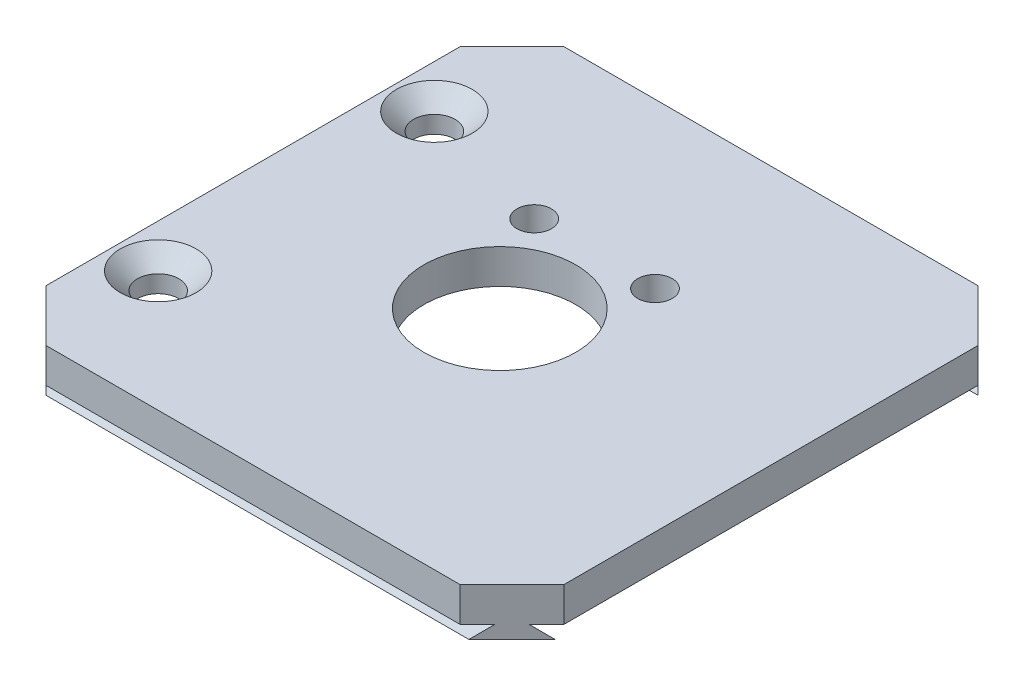
SolidWorks part; units mm, degrees
ref_plane "Front Plane" through (0, 0, 0) normal (0, 0, 1) x (1, 0, 0)
ref_plane "Top Plane" through (0, 0, 0) normal (0, 1, 0) x (1, 0, 0)
ref_plane "Right Plane" through (0, 0, 0) normal (1, 0, 0) x (0, 0, -1)
sketch "Sketch1" plane through (0, 0, 0) normal (0, 1, 0) x (1, 0, 0)
  line L0 (-11.2931, 29.7045) -> (12.7069, 29.7045)
  line L1 (12.7069, 29.7045) -> (15.7069, 26.7045)
  line L2 (15.7069, 26.7045) -> (15.7069, 2.7045)
  line L3 (15.7069, 2.7045) -> (12.7069, -0.2955)
  line L4 (12.7069, -0.2955) -> (-11.2931, -0.2955)
  line L5 (-11.2931, -0.2955) -> (-14.2931, 2.7045)
  line L6 (-14.2931, 26.7045) -> (-14.2931, 2.7045)
  line L7 (-11.2931, 29.7045) -> (-14.2931, 26.7045)
extrude "Boss-Extrude1" add sketch "Sketch1" along normal blind 2
sketch "Sketch2" plane through (0, 2, 0) normal (0, 1, 0) x (1, 0, 0)
  circle A0 centre (0, 14.7045) radius 4.4
  dimension "D1" = 8.8
extrude "Cut-Extrude1" cut sketch "Sketch2" against normal through all
sketch "Sketch5" plane through (0, 2, 0) normal (0, 1, 0) x (1, 0, 0)
  line L0 (-14.2931, 26.7045) -> (-14.2931, 2.7045) construction
  circle A0 centre (-3.5084, 20.2045) radius 1
  circle A1 centre (3.4916, 20.2045) radius 1
  dimension "D1" = 2
  dimension "D2" = 10.7846
  dimension "D3" = 17.7846
  dimension "D4" = 6.5
extrude "Cut-Extrude2" cut sketch "Sketch5" against normal up to next
sketch "Sketch7" plane through (0, 2, 0) normal (0, 1, 0) x (1, 0, 0)
  line L0 (12.7069, 29.7045) -> (-11.2931, 29.7045) construction
  line L1 (-11.2931, -0.2955) -> (12.7069, -0.2955) construction
  line L3 (-14.2931, 26.7045) -> (-14.2931, 2.7045) construction
  circle A0 centre (-11.7931, 22.7045) radius 1
  circle A1 centre (-11.7931, 6.7045) radius 1
  point P0 (-11.7931, 22.7045)
  point P2 (-11.7931, 6.7045)
  dimension "D5" = 2
  dimension "D6" = 2
  dimension "D1" = 7
  dimension "D2" = 7
  dimension "D3" = 2.5
  dimension "D4" = 2.5
hole_wizard "CSK for M2 Flat Head Machine Screw2" positions "Sketch7" profile "Sketch8" countersink size "M2" standard "ANSI Metric"
sketch "Sketch8" plane through (-11.7931, 2, -22.7045) normal (1, 0, 0) x (0, 0, 1)
  line L0 (0, 0) -> (0, 43.651)
  line L1 (0, 43.651) -> (1.2, 42.93)
  line L2 (1.2, 42.93) -> (1.2, 1)
  line L3 (1.2, 1) -> (2.2, 0)
  line L5 (2.2, 0) -> (0, 0)
  line L6 (-1.2, 1) -> (-2.2, 0) construction
  line L10 (0, 43.651) -> (-1.2, 42.93) construction
  line L11 (0, -6.35) -> (0, 107.95) construction
  dimension "Hole Dia." = 2.4
  dimension "Hole Depth" = 42.93
  dimension "Near C'Sink Dia." = 4.4
  dimension "Near C'Sink Angle" = 90
  dimension "Drill Angle" = 118
sketch "Sketch10" plane through (15.7069, 0, 0) normal (1, 0, 0) x (0, 0, -1)
  line L0 (14.7045, 2) -> (14.7045, 0) construction
  line L1 (2.7045, 2) -> (26.7045, 2) construction
  line L2 (2.7045, 0) -> (26.7045, 0) construction
  line L3 (1.7045, 0) -> (2.4545, -0.75)
  line L4 (2.4545, -0.75) -> (-0.0455, -0.75)
  line L5 (-0.0455, -0.75) -> (0.7045, 0)
  line L6 (0.7045, 0) -> (1.7045, 0)
  line L8 (28.7045, 0) -> (27.7045, 0)
  line L9 (29.4545, -0.75) -> (28.7045, 0)
  line L10 (26.9545, -0.75) -> (29.4545, -0.75)
  line L11 (27.7045, 0) -> (26.9545, -0.75)
  dimension "D1" = 1
  dimension "D2" = 1
  dimension "D3" = 45
  dimension "D4" = 45
  dimension "D5" = 2.5
  dimension "D6" = 1
extrude "Boss-Extrude2" add sketch "Sketch10" against normal up to surface (30 mm away) up to face at (-14.2931, 1, -14.7045)
sketch "Sketch11" plane through (0, 2, 0) normal (0, 1, 0) x (1, 0, 0)
  line L0 (-14.2931, 26.7045) -> (-11.2931, 29.7045)
  line L1 (-11.2931, 29.7045) -> (12.7069, 29.7045)
  line L2 (12.7069, 29.7045) -> (15.7069, 26.7045)
  line L3 (15.7069, 26.7045) -> (15.7069, 2.7045)
  line L4 (15.7069, 2.7045) -> (12.7069, -0.2955)
  line L5 (12.7069, -0.2955) -> (-11.2931, -0.2955)
  line L6 (-11.2931, -0.2955) -> (-14.2931, 2.7045)
  line L7 (-14.2931, 2.7045) -> (-14.2931, 26.7045)
  line L8 (-24.2931, -1.4376) -> (-24.2931, 30.8467)
  line L9 (-24.2931, 30.8467) -> (-15.4352, 39.7045)
  line L10 (-15.4352, 39.7045) -> (16.8491, 39.7045)
  line L11 (16.8491, 39.7045) -> (25.7069, 30.8467)
  line L12 (25.7069, 30.8467) -> (25.7069, -1.4376)
  line L13 (25.7069, -1.4376) -> (16.8491, -10.2955)
  line L14 (16.8491, -10.2955) -> (-15.4352, -10.2955)
  line L15 (-15.4352, -10.2955) -> (-24.2931, -1.4376)
  point P24 (15.7069, 2.4545)
  point P25 (15.7069, 2.7045)
  dimension "D1" = 10
extrude "Cut-Extrude3" cut sketch "Sketch11" against normal through all
